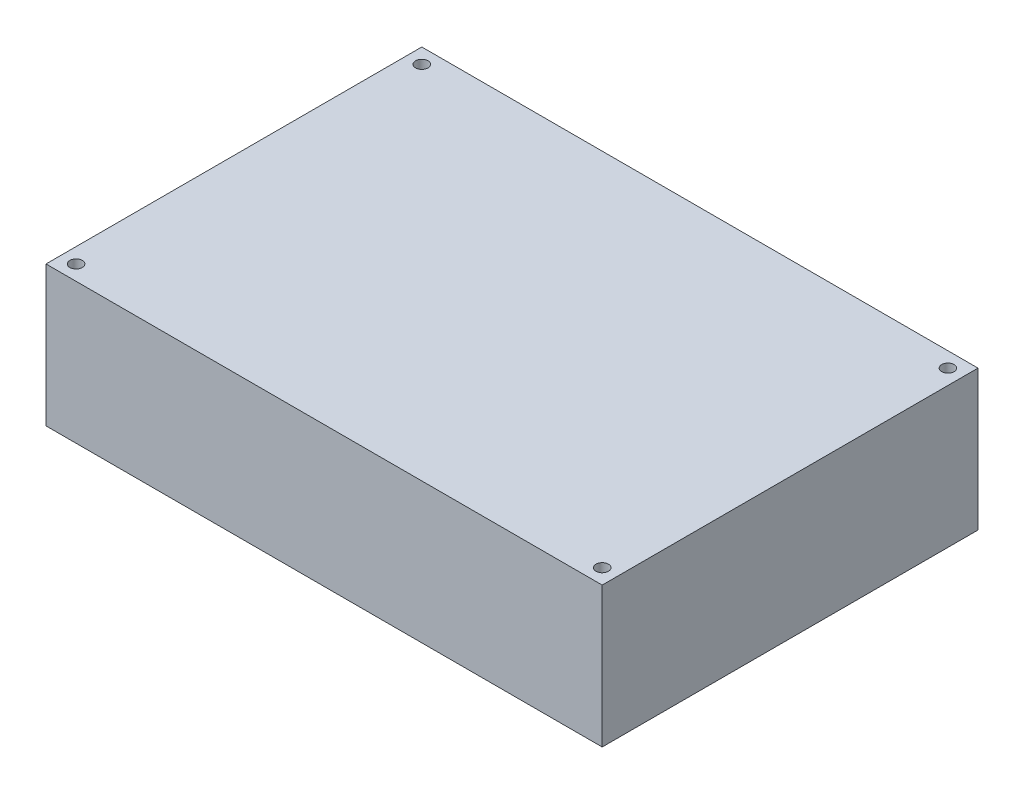
SolidWorks part; units mm, degrees
ref_plane "前视基准面" through (0, 0, 0) normal (0, 0, 1) x (1, 0, 0)
ref_plane "上视基准面" through (0, 0, 0) normal (0, 1, 0) x (1, 0, 0)
ref_plane "右视基准面" through (0, 0, 0) normal (1, 0, 0) x (0, 0, -1)
other "Configuration Table"
sketch "草图1" plane through (0, 0, 0) normal (0, 1, 0) x (1, 0, 0)
  line L0 (-44.45, 29.21) -> (44.45, -29.21) construction
  line L1 (-46.99, -31.75) -> (46.99, -31.75)
  line L2 (-46.99, -31.75) -> (-46.99, 31.75)
  line L3 (-46.99, 31.75) -> (46.99, 31.75)
  line L4 (46.99, -31.75) -> (46.99, 31.75)
  line L5 (-46.99, -31.75) -> (46.99, 31.75) construction
  line L6 (-46.99, 31.75) -> (46.99, -31.75) construction
  circle A1 centre (-44.45, 29.21) radius 1.05
  circle A3 centre (-44.45, -29.21) radius 1.05
  circle A5 centre (44.45, 29.21) radius 1.05
  circle A7 centre (44.45, -29.21) radius 1.05
  point P0 (0, 0)
  dimension "D3" = 2.1
  dimension "D4" = 2.54
  dimension "D1" = 93.98
  dimension "D2" = 88.9
  dimension "D5" = 63.5
extrude "凸台-拉伸1" add sketch "草图1" along normal blind 1.7 contours L3 L4 L1 L2 | A1 | A5 | A7 | A3
extrude "凸台-拉伸2" add sketch "草图1<4>" along normal blind 22 from surface starting at face at (0, 1.7, 0)
sketch "草图1<4>" plane through (0, 0, 0) normal (0, 1, 0) x (1, 0, 0) same geometry as "草图1"
